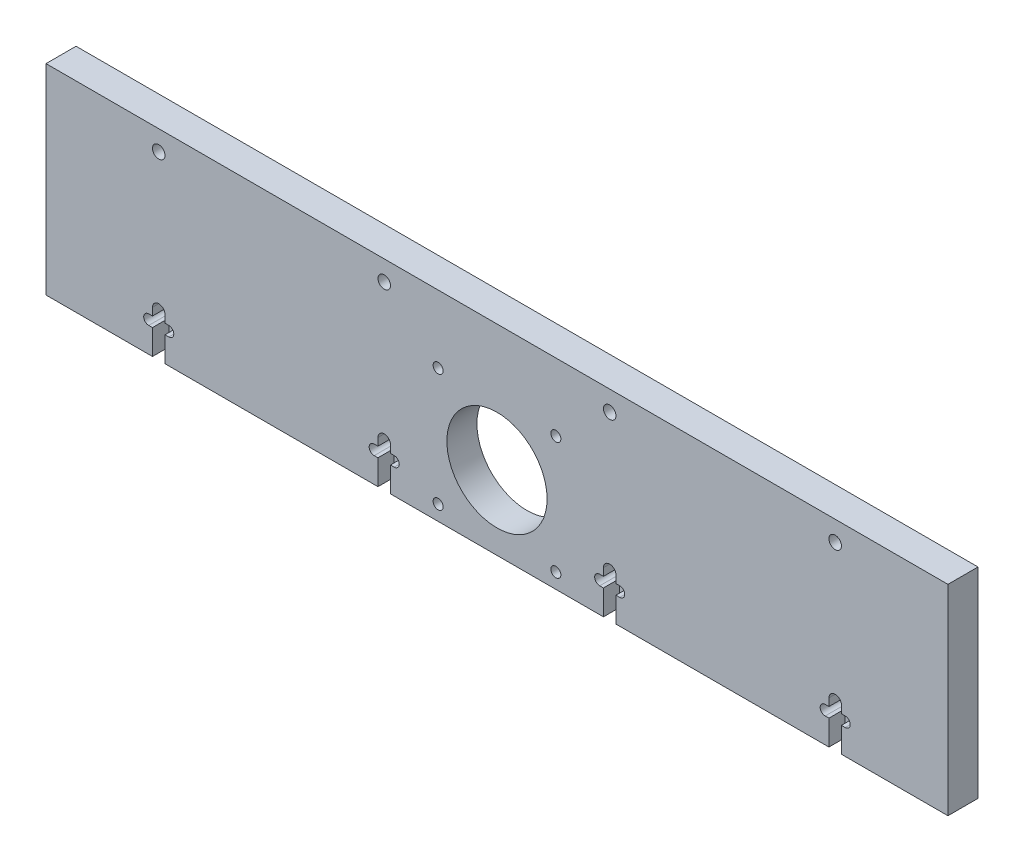
SolidWorks part; units mm, degrees
material "HDPE-green"
ref_plane "Front Plane" through (0, 0, 0) normal (0, 0, 1) x (1, 0, 0)
ref_plane "Top Plane" through (0, 0, 0) normal (0, 1, 0) x (1, 0, 0)
ref_plane "Right Plane" through (0, 0, 0) normal (1, 0, 0) x (0, 0, -1)
sketch "Sketch1" plane through (0, 0, 0) normal (0, 0, 1) x (1, 0, 0)
  line L1 (-180, -40) -> (180, -40)
  line L2 (-180, -40) -> (-180, 40)
  line L3 (-180, 40) -> (180, 40)
  line L4 (180, -40) -> (180, 40)
  line L5 (-180, -40) -> (180, 40) construction
  line L6 (-180, 40) -> (180, -40) construction
  point P0 (0, 0)
extrude "Boss-Extrude1" add sketch "Sketch1" along normal blind 12
sketch "Sketch2" plane through (0, 0, 12) normal (0, 0, 1) x (1, 0, 0)
  line L0 (180, -40) -> (180, 40) construction
  line L1 (180, 40) -> (-180, 40) construction
  circle A0 centre (135, 32) radius 2.5
  dimension "D1" = 5
  dimension "D2" = 45
  dimension "D3" = 8
extrude "Cut-Extrude1" cut sketch "Sketch2" against normal up to next
sketch "Sketch6" plane through (-192.1398, 109.5567, 12) normal (0, 0, 1) x (1, 0, 0)
  line L0 (323.1398, -137.5567) -> (331.1398, -137.5567) construction
  line L1 (323.1398, -135.5567) -> (331.1398, -135.5567)
  line L2 (323.1398, -139.5567) -> (331.1398, -139.5567)
  line L3 (12.1398, -149.5567) -> (372.1398, -149.5567) construction
  arc A0 (323.1398, -135.5567) -> (323.1398, -139.5567) centre (323.1398, -137.5567) ccw
  arc A1 (331.1398, -139.5567) -> (331.1398, -135.5567) centre (331.1398, -137.5567) ccw
  point P2 (327.1398, -137.5567)
  dimension "D1" = 8
  dimension "D2" = 135
  dimension "D4" = 12
extrude "Cut-Extrude4" cut sketch "Sketch6" against normal blind 8
sketch "Sketch8" plane through (-192.1398, 109.5567, 12) normal (0, 0, 1) x (1, 0, 0)
  line L0 (327.1398, -132.5567) -> (327.1398, -186.1866) construction
  line L1 (329.6398, -132.5567) -> (329.6398, -186.1866)
  line L2 (324.6398, -132.5567) -> (324.6398, -186.1866)
  line L3 (12.1398, -149.5567) -> (372.1398, -149.5567) construction
  arc A0 (329.6398, -132.5567) -> (324.6398, -132.5567) centre (327.1398, -132.5567) ccw
  arc A1 (324.6398, -186.1866) -> (329.6398, -186.1866) centre (327.1398, -186.1866) ccw
  point P2 (327.1398, -159.3717)
  dimension "D1" = 17
  dimension "D2" = 2.5
  dimension "D3" = 135
extrude "Cut-Extrude5" cut sketch "Sketch8" against normal blind 6.5
pattern_linear "LPattern1" count 4 spacing 90 along (-1, 0, 0) of "Cut-Extrude1", "Cut-Extrude4", "Cut-Extrude5"
sketch "Sketch3" plane through (0, 0, 12) normal (0, 0, 1) x (1, 0, 0)
  line L0 (-180, -40) -> (-137.5, -40) construction
  circle A0 centre (0, -10.5) radius 20
  dimension "D1" = 40
  dimension "D2" = 29.5
extrude "Cut-Extrude2" cut sketch "Sketch3" against normal up to next
sketch "Sketch4" plane through (0, 0, 12) normal (0, 0, 1) x (1, 0, 0)
  line L0 (0, 17.4189) -> (0, -17.4926) construction
  line L1 (-17.6695, 0) -> (16.7711, 0) construction
  circle A0 centre (-23.5, 13) radius 2
  circle A1 centre (0, -10.5) radius 20 construction
  circle A2 centre (-23.5, -34) radius 2
  dimension "D1" = 4
  dimension "D2" = 23.5
  dimension "D3" = 23.5
  dimension "D4" = 4
  dimension "D5" = 23.5
  dimension "D6" = 23.5
extrude "Cut-Extrude3" cut sketch "Sketch4" against normal up to next
mirror "Mirror2" about plane through (0, 0, 0) normal (1, 0, 0) of "Cut-Extrude3"
